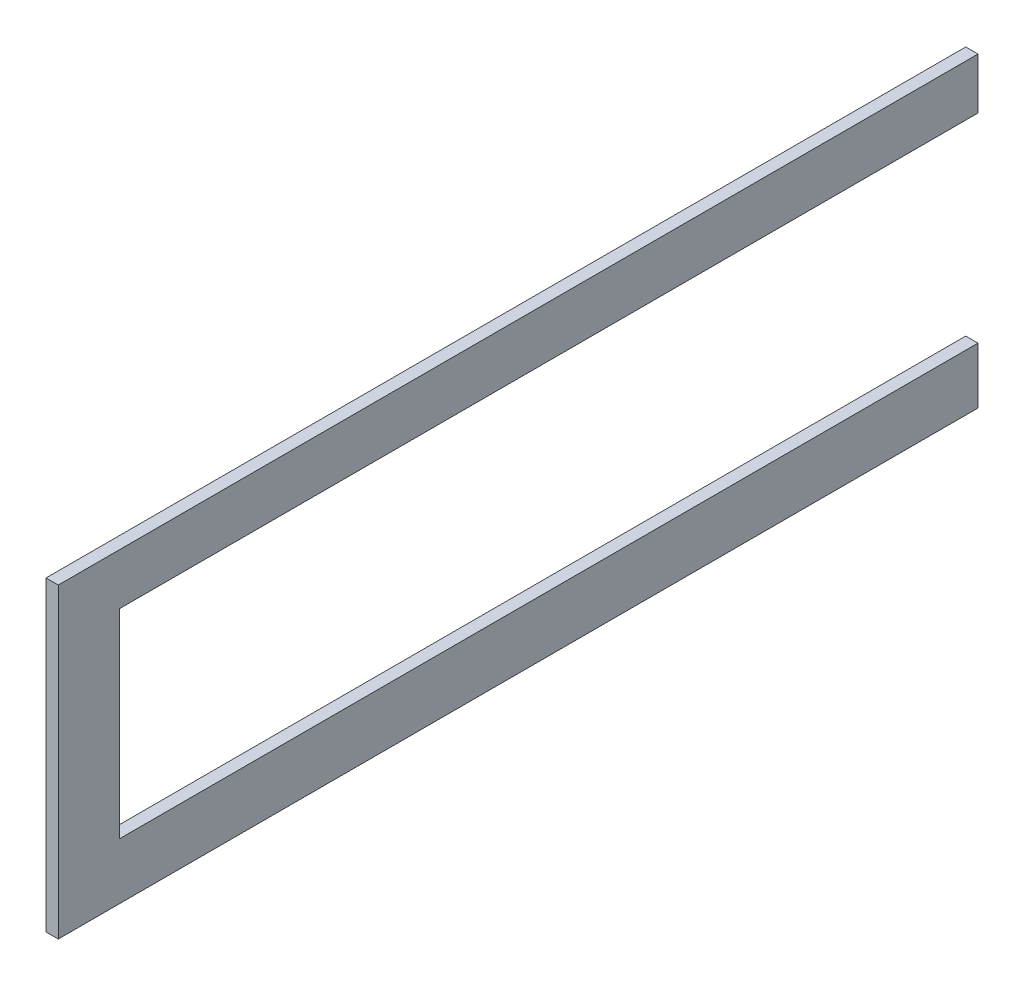
SolidWorks part; units mm, degrees
ref_plane "Front" through (0, 0, 0) normal (0, 0, 1) x (1, 0, 0)
ref_plane "Top" through (0, 0, 0) normal (0, 1, 0) x (1, 0, 0)
ref_plane "Right" through (0, 0, 0) normal (1, 0, 0) x (0, 0, -1)
sketch "Sketch1" plane through (0, 0, 0) normal (1, 0, 0) x (0, 0, -1)
  line L0 (450, 125) -> (450, 150)
  line L1 (0, 0) -> (450, 0)
  line L2 (0, 0) -> (0, 150)
  line L3 (0, 150) -> (450, 150)
  line L4 (450, 0) -> (450, 27.5)
  line L5 (450, 125) -> (30, 125)
  line L7 (450, 27.5) -> (30, 27.5)
  line L8 (30, 125) -> (30, 27.5)
  dimension "D1" = 420
  dimension "D2" = 150
  dimension "D3" = 27.5
  dimension "D4" = 25
  dimension "D5" = 30
extrude "Boss-Extrude1" add sketch "Sketch1" along normal blind 6
